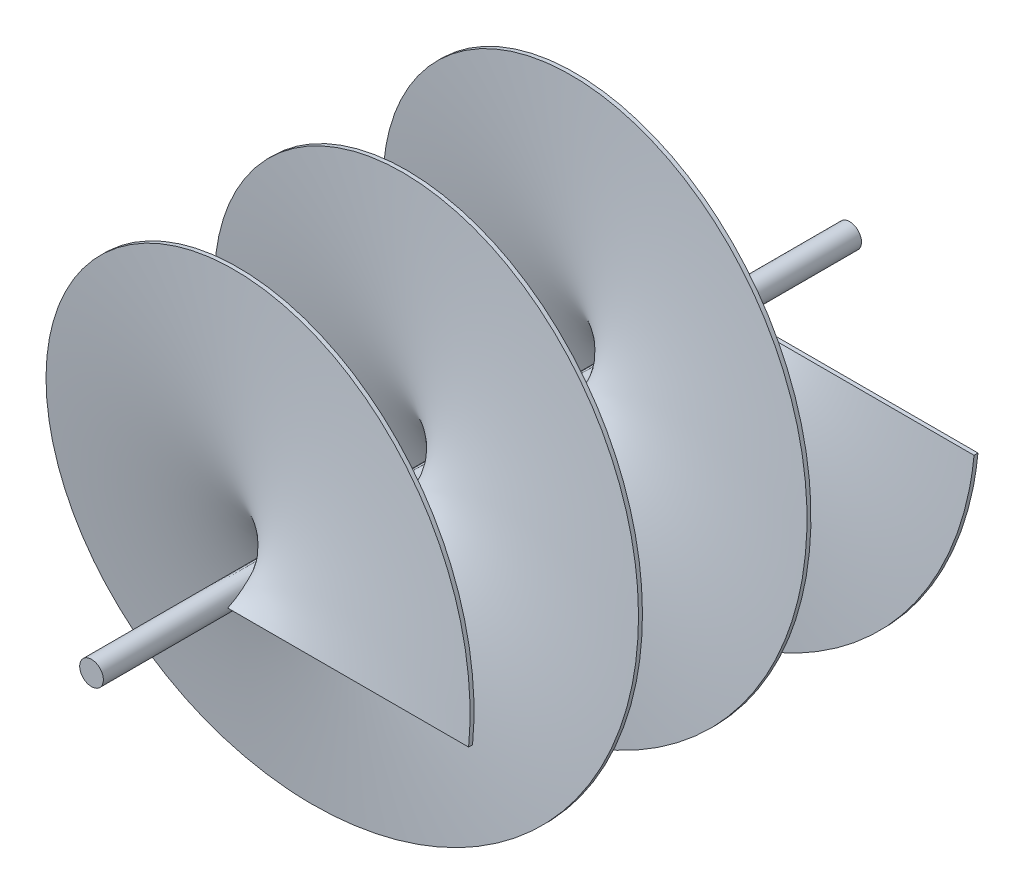
SolidWorks part; units mm, degrees
material "Plain Carbon Steel"
ref_plane "Front Plane" through (0, 0, 0) normal (0, 0, 1) x (1, 0, 0)
ref_plane "Top Plane" through (0, 0, 0) normal (0, 1, 0) x (1, 0, 0)
ref_plane "Right Plane" through (0, 0, 0) normal (1, 0, 0) x (0, 0, -1)
sketch "Sketch1" plane through (0, 0, 0) normal (0, 0, 1) x (1, 0, 0)
  circle A0 centre (0, 0) radius 9.525
  dimension "D1" = 19.05
extrude "Boss-Extrude1" add sketch "Sketch1" along normal blind 609.6
ref_plane "Plane1" through (0, 0, 508) normal (0, 0, 1) x (1, 0, 0)
sketch "Sketch2" plane through (0, 0, 508) normal (0, 0, 1) x (1, 0, 0)
  circle A0 centre (0, 0) radius 203.2
  dimension "D1" = 406.4
curve "Helix/Spiral1" pitch 135.4667 height 406.4 radius 203.2 left hand yes centre (0, 0, 508) axis (0, 0, -1) start towards (1, 0, 0)
sketch "Sketch3" plane through (0, 0, 0) normal (0, 1, 0) x (1, 0, 0)
  line L0 (-9.525, 0) -> (-9.525, -609.6) construction
  line L1 (-9.525, -509.5875) -> (203.2, -509.5875)
  line L2 (-9.525, -509.5875) -> (-9.525, -506.4125)
  line L3 (-9.525, -506.4125) -> (203.2, -506.4125)
  line L4 (203.2, -509.5875) -> (203.2, -506.4125)
  spline S0 degree 3 poles (-795.7118, -553.8828) (-91.6333, -551.3817) (233.2801, -527.8361) (199.5403, -503.7221) (194.5854, -501.5831) (187.717, -499.4442) (179.0025, -497.3053) (168.5276, -495.1663) (156.3954, -493.0274) (142.7252, -490.8884) (127.6515, -488.7495) (111.3223, -486.6105) (93.8984, -484.4716) (75.5511, -482.3326) (56.4608, -480.1937) (36.8153, -478.0547) (16.8077, -475.9158) (-3.3652, -473.7768) (-23.505, -471.6379) (-43.4136, -469.4989) (-62.8953, -467.36) (-81.7585, -465.2211) (-99.8177, -463.0821) (-116.8952, -460.9432) (-132.8231, -458.8042) (-147.4449, -456.6653) (-160.6166, -454.5263) (-172.2088, -452.3874) (-182.1075, -450.2484) (-190.2153, -448.1095) (-196.4524, -445.9705) (-200.7577, -443.8316) (-203.0886, -441.6926) (-203.4223, -439.5537) (-201.7555, -437.4147) (-198.1047, -435.2758) (-192.5056, -433.1368) (-185.0134, -430.9979) (-175.7017, -428.8589) (-164.6621, -426.72) (-152.0033, -424.5811) (-137.8496, -422.4421) (-122.3402, -420.3032) (-105.6277, -418.1642) (-87.8765, -416.0253) (-69.2611, -413.8863) (-49.9645, -411.7474) (-30.1766, -409.6084) (-10.092, -407.4695) (10.092, -405.3305) (30.1766, -403.1916) (49.9645, -401.0526) (69.2611, -398.9137) (87.8765, -396.7747) (105.6277, -394.6358) (122.3402, -392.4968) (137.8496, -390.3579) (152.0033, -388.2189) (164.6621, -386.08) (175.7017, -383.9411) (185.0134, -381.8021) (192.5056, -379.6632) (198.1047, -377.5242) (201.7555, -375.3853) (203.4223, -373.2463) (203.0886, -371.1074) (200.7577, -368.9684) (196.4524, -366.8295) (190.2153, -364.6905) (182.1075, -362.5516) (172.2088, -360.4126) (160.6166, -358.2737) (147.4449, -356.1347) (132.8231, -353.9958) (116.8952, -351.8568) (99.8177, -349.7179) (81.7585, -347.5789) (62.8953, -345.44) (43.4136, -343.3011) (23.505, -341.1621) (3.3652, -339.0232) (-16.8077, -336.8842) (-36.8153, -334.7453) (-56.4608, -332.6063) (-75.5511, -330.4674) (-93.8984, -328.3284) (-111.3223, -326.1895) (-127.6515, -324.0505) (-142.7252, -321.9116) (-156.3954, -319.7726) (-168.5276, -317.6337) (-179.0025, -315.4947) (-187.717, -313.3558) (-194.5854, -311.2168) (-199.5403, -309.0779) (-202.5328, -306.9389) (-203.5336, -304.8) (-202.5328, -302.6611) (-199.5403, -300.5221) (-194.5854, -298.3832) (-187.717, -296.2442) (-179.0025, -294.1053) (-168.5276, -291.9663) (-156.3954, -289.8274) (-142.7252, -287.6884) (-127.6515, -285.5495) (-111.3223, -283.4105) (-93.8984, -281.2716) (-75.5511, -279.1326) (-56.4608, -276.9937) (-36.8153, -274.8547) (-16.8077, -272.7158) (3.3652, -270.5768) (23.505, -268.4379) (43.4136, -266.2989) (62.8953, -264.16) (81.7585, -262.0211) (99.8177, -259.8821) (116.8952, -257.7432) (132.8231, -255.6042) (147.4449, -253.4653) (160.6166, -251.3263) (172.2088, -249.1874) (182.1075, -247.0484) (190.2153, -244.9095) (196.4524, -242.7705) (200.7577, -240.6316) (203.0886, -238.4926) (203.4223, -236.3537) (201.7555, -234.2147) (198.1047, -232.0758) (192.5056, -229.9368) (185.0134, -227.7979) (175.7017, -225.6589) (164.6621, -223.52) (152.0033, -221.3811) (137.8496, -219.2421) (122.3402, -217.1032) (105.6277, -214.9642) (87.8765, -212.8253) (69.2611, -210.6863) (49.9645, -208.5474) (30.1766, -206.4084) (10.092, -204.2695) (-10.092, -202.1305) (-30.1766, -199.9916) (-49.9645, -197.8526) (-69.2611, -195.7137) (-87.8765, -193.5747) (-105.6277, -191.4358) (-122.3402, -189.2968) (-137.8496, -187.1579) (-152.0033, -185.0189) (-164.6621, -182.88) (-175.7017, -180.7411) (-185.0134, -178.6021) (-192.5056, -176.4632) (-198.1047, -174.3242) (-201.7555, -172.1853) (-203.4223, -170.0463) (-203.0886, -167.9074) (-200.7577, -165.7684) (-196.4524, -163.6295) (-190.2153, -161.4905) (-182.1075, -159.3516) (-172.2088, -157.2126) (-160.6166, -155.0737) (-147.4449, -152.9347) (-132.8231, -150.7958) (-116.8952, -148.6568) (-99.8177, -146.5179) (-81.7585, -144.3789) (-62.8953, -142.24) (-43.4136, -140.1011) (-23.505, -137.9621) (-3.3652, -135.8232) (16.8077, -133.6842) (36.8153, -131.5453) (56.4608, -129.4063) (75.5511, -127.2674) (93.8984, -125.1284) (111.3223, -122.9895) (127.6515, -120.8505) (142.7252, -118.7116) (156.3954, -116.5726) (168.5276, -114.4337) (179.0025, -112.2947) (187.717, -110.1558) (194.5854, -108.0169) (199.5403, -105.8779) (233.2791, -81.7646) (-91.612, -58.2198) (-795.6403, -55.7175) knots -0.162231 -0.162231 -0.162231 -0.162231 0.005263 0.010526 0.015789 0.021053 0.026316 0.031579 0.036842 0.042105 0.047368 0.052632 0.057895 0.063158 0.068421 0.073684 0.078947 0.084211 0.089474 0.094737 0.1 0.105263 0.110526 0.115789 0.121053 0.126316 0.131579 0.136842 0.142105 0.147368 0.152632 0.157895 0.163158 0.168421 0.173684 0.178947 0.184211 0.189474 0.194737 0.2 0.205263 0.210526 0.215789 0.221053 0.226316 0.231579 0.236842 0.242105 0.247368 0.252632 0.257895 0.263158 0.268421 0.273684 0.278947 0.284211 0.289474 0.294737 0.3 0.305263 0.310526 0.315789 0.321053 0.326316 0.331579 0.336842 0.342105 0.347368 0.352632 0.357895 0.363158 0.368421 0.373684 0.378947 0.384211 0.389474 0.394737 0.4 0.405263 0.410526 0.415789 0.421053 0.426316 0.431579 0.436842 0.442105 0.447368 0.452632 0.457895 0.463158 0.468421 0.473684 0.478947 0.484211 0.489474 0.494737 0.5 0.505263 0.510526 0.515789 0.521053 0.526316 0.531579 0.536842 0.542105 0.547368 0.552632 0.557895 0.563158 0.568421 0.573684 0.578947 0.584211 0.589474 0.594737 0.6 0.605263 0.610526 0.615789 0.621053 0.626316 0.631579 0.636842 0.642105 0.647368 0.652632 0.657895 0.663158 0.668421 0.673684 0.678947 0.684211 0.689474 0.694737 0.7 0.705263 0.710526 0.715789 0.721053 0.726316 0.731579 0.736842 0.742105 0.747368 0.752632 0.757895 0.763158 0.768421 0.773684 0.778947 0.784211 0.789474 0.794737 0.8 0.805263 0.810526 0.815789 0.821053 0.826316 0.831579 0.836842 0.842105 0.847368 0.852632 0.857895 0.863158 0.868421 0.873684 0.878947 0.884211 0.889474 0.894737 0.9 0.905263 0.910526 0.915789 0.921053 0.926316 0.931579 0.936842 0.942105 0.947368 0.952632 0.957895 0.963158 0.968421 0.973684 0.978947 0.984211 0.989474 0.994737 1.162226 1.162226 1.162226 1.162226 only from (203.2, -508) to (203.2, -101.6) construction
  spline S1 degree 3 poles (203.2, -508) (203.2, -507.2873) (202.5328, -505.8609) (199.5403, -503.7221) (194.5854, -501.5831) (187.717, -499.4442) (179.0025, -497.3053) (168.5276, -495.1663) (156.3954, -493.0274) (142.7252, -490.8884) (127.6515, -488.7495) (111.3223, -486.6105) (93.8984, -484.4716) (75.5511, -482.3326) (56.4608, -480.1937) (36.8153, -478.0547) (16.8077, -475.9158) (-3.3652, -473.7768) (-23.505, -471.6379) (-43.4136, -469.4989) (-62.8953, -467.36) (-81.7585, -465.2211) (-99.8177, -463.0821) (-116.8952, -460.9432) (-132.8231, -458.8042) (-147.4449, -456.6653) (-160.6166, -454.5263) (-172.2088, -452.3874) (-182.1075, -450.2484) (-190.2153, -448.1095) (-196.4524, -445.9705) (-200.7577, -443.8316) (-203.0886, -441.6926) (-203.4223, -439.5537) (-201.7555, -437.4147) (-198.1047, -435.2758) (-192.5056, -433.1368) (-185.0134, -430.9979) (-175.7017, -428.8589) (-164.6621, -426.72) (-152.0033, -424.5811) (-137.8496, -422.4421) (-122.3402, -420.3032) (-105.6277, -418.1642) (-87.8765, -416.0253) (-69.2611, -413.8863) (-49.9645, -411.7474) (-30.1766, -409.6084) (-10.092, -407.4695) (10.092, -405.3305) (30.1766, -403.1916) (49.9645, -401.0526) (69.2611, -398.9137) (87.8765, -396.7747) (105.6277, -394.6358) (122.3402, -392.4968) (137.8496, -390.3579) (152.0033, -388.2189) (164.6621, -386.08) (175.7017, -383.9411) (185.0134, -381.8021) (192.5056, -379.6632) (198.1047, -377.5242) (201.7555, -375.3853) (203.4223, -373.2463) (203.0886, -371.1074) (200.7577, -368.9684) (196.4524, -366.8295) (190.2153, -364.6905) (182.1075, -362.5516) (172.2088, -360.4126) (160.6166, -358.2737) (147.4449, -356.1347) (132.8231, -353.9958) (116.8952, -351.8568) (99.8177, -349.7179) (81.7585, -347.5789) (62.8953, -345.44) (43.4136, -343.3011) (23.505, -341.1621) (3.3652, -339.0232) (-16.8077, -336.8842) (-36.8153, -334.7453) (-56.4608, -332.6063) (-75.5511, -330.4674) (-93.8984, -328.3284) (-111.3223, -326.1895) (-127.6515, -324.0505) (-142.7252, -321.9116) (-156.3954, -319.7726) (-168.5276, -317.6337) (-179.0025, -315.4947) (-187.717, -313.3558) (-194.5854, -311.2168) (-199.5403, -309.0779) (-202.5328, -306.9389) (-203.5336, -304.8) (-202.5328, -302.6611) (-199.5403, -300.5221) (-194.5854, -298.3832) (-187.717, -296.2442) (-179.0025, -294.1053) (-168.5276, -291.9663) (-156.3954, -289.8274) (-142.7252, -287.6884) (-127.6515, -285.5495) (-111.3223, -283.4105) (-93.8984, -281.2716) (-75.5511, -279.1326) (-56.4608, -276.9937) (-36.8153, -274.8547) (-16.8077, -272.7158) (3.3652, -270.5768) (23.505, -268.4379) (43.4136, -266.2989) (62.8953, -264.16) (81.7585, -262.0211) (99.8177, -259.8821) (116.8952, -257.7432) (132.8231, -255.6042) (147.4449, -253.4653) (160.6166, -251.3263) (172.2088, -249.1874) (182.1075, -247.0484) (190.2153, -244.9095) (196.4524, -242.7705) (200.7577, -240.6316) (203.0886, -238.4926) (203.4223, -236.3537) (201.7555, -234.2147) (198.1047, -232.0758) (192.5056, -229.9368) (185.0134, -227.7979) (175.7017, -225.6589) (164.6621, -223.52) (152.0033, -221.3811) (137.8496, -219.2421) (122.3402, -217.1032) (105.6277, -214.9642) (87.8765, -212.8253) (69.2611, -210.6863) (49.9645, -208.5474) (30.1766, -206.4084) (10.092, -204.2695) (-10.092, -202.1305) (-30.1766, -199.9916) (-49.9645, -197.8526) (-69.2611, -195.7137) (-87.8765, -193.5747) (-105.6277, -191.4358) (-122.3402, -189.2968) (-137.8496, -187.1579) (-152.0033, -185.0189) (-164.6621, -182.88) (-175.7017, -180.7411) (-185.0134, -178.6021) (-192.5056, -176.4632) (-198.1047, -174.3242) (-201.7555, -172.1853) (-203.4223, -170.0463) (-203.0886, -167.9074) (-200.7577, -165.7684) (-196.4524, -163.6295) (-190.2153, -161.4905) (-182.1075, -159.3516) (-172.2088, -157.2126) (-160.6166, -155.0737) (-147.4449, -152.9347) (-132.8231, -150.7958) (-116.8952, -148.6568) (-99.8177, -146.5179) (-81.7585, -144.3789) (-62.8953, -142.24) (-43.4136, -140.1011) (-23.505, -137.9621) (-3.3652, -135.8232) (16.8077, -133.6842) (36.8153, -131.5453) (56.4608, -129.4063) (75.5511, -127.2674) (93.8984, -125.1284) (111.3223, -122.9895) (127.6515, -120.8505) (142.7252, -118.7116) (156.3954, -116.5726) (168.5276, -114.4337) (179.0025, -112.2947) (187.717, -110.1558) (194.5854, -108.0169) (199.5403, -105.8779) (202.5328, -103.7391) (203.2, -102.3127) (203.2, -101.6) knots 0 0 0 0 0.005263 0.010526 0.015789 0.021053 0.026316 0.031579 0.036842 0.042105 0.047368 0.052632 0.057895 0.063158 0.068421 0.073684 0.078947 0.084211 0.089474 0.094737 0.1 0.105263 0.110526 0.115789 0.121053 0.126316 0.131579 0.136842 0.142105 0.147368 0.152632 0.157895 0.163158 0.168421 0.173684 0.178947 0.184211 0.189474 0.194737 0.2 0.205263 0.210526 0.215789 0.221053 0.226316 0.231579 0.236842 0.242105 0.247368 0.252632 0.257895 0.263158 0.268421 0.273684 0.278947 0.284211 0.289474 0.294737 0.3 0.305263 0.310526 0.315789 0.321053 0.326316 0.331579 0.336842 0.342105 0.347368 0.352632 0.357895 0.363158 0.368421 0.373684 0.378947 0.384211 0.389474 0.394737 0.4 0.405263 0.410526 0.415789 0.421053 0.426316 0.431579 0.436842 0.442105 0.447368 0.452632 0.457895 0.463158 0.468421 0.473684 0.478947 0.484211 0.489474 0.494737 0.5 0.505263 0.510526 0.515789 0.521053 0.526316 0.531579 0.536842 0.542105 0.547368 0.552632 0.557895 0.563158 0.568421 0.573684 0.578947 0.584211 0.589474 0.594737 0.6 0.605263 0.610526 0.615789 0.621053 0.626316 0.631579 0.636842 0.642105 0.647368 0.652632 0.657895 0.663158 0.668421 0.673684 0.678947 0.684211 0.689474 0.694737 0.7 0.705263 0.710526 0.715789 0.721053 0.726316 0.731579 0.736842 0.742105 0.747368 0.752632 0.757895 0.763158 0.768421 0.773684 0.778947 0.784211 0.789474 0.794737 0.8 0.805263 0.810526 0.815789 0.821053 0.826316 0.831579 0.836842 0.842105 0.847368 0.852632 0.857895 0.863158 0.868421 0.873684 0.878947 0.884211 0.889474 0.894737 0.9 0.905263 0.910526 0.915789 0.921053 0.926316 0.931579 0.936842 0.942105 0.947368 0.952632 0.957895 0.963158 0.968421 0.973684 0.978947 0.984211 0.989474 0.994737 1 1 1 1 construction
  point P8 (203.2, -508)
  dimension "D1" = 3.175
sweep "Sweep1" add profiles "Sketch3" path "Helix/Spiral1"
